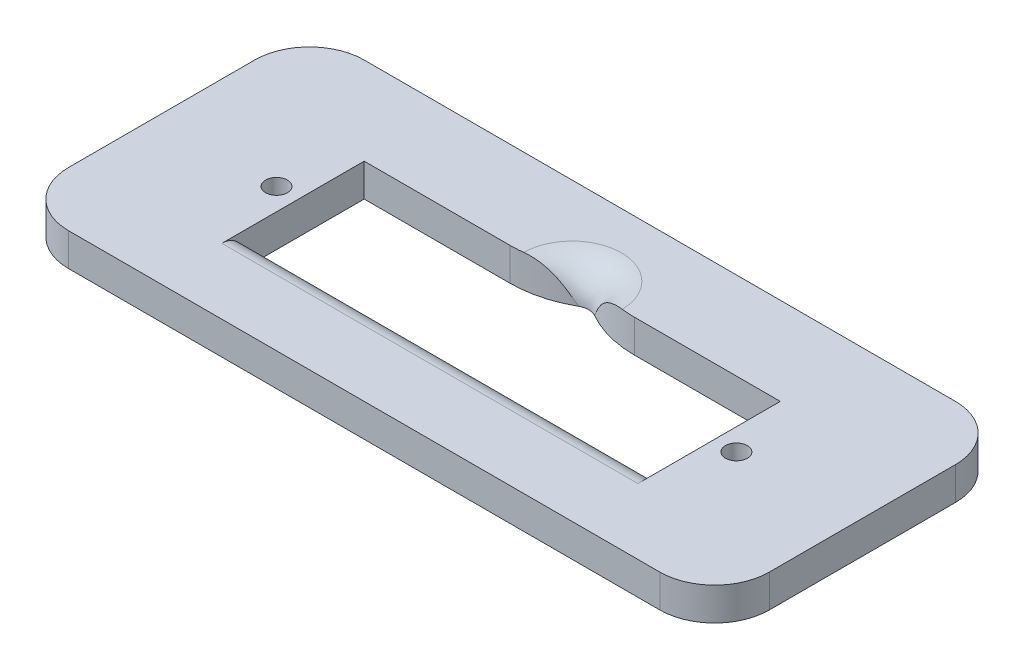
SolidWorks part; units mm, degrees
ref_plane "Front Plane" through (0, 0, 0) normal (0, 0, 1) x (1, 0, 0)
ref_plane "Top Plane" through (0, 0, 0) normal (0, 1, 0) x (1, 0, 0)
ref_plane "Right Plane" through (0, 0, 0) normal (1, 0, 0) x (0, 0, -1)
sketch "Sketch1" plane through (0, 0, 0) normal (0, 1, 0) x (1, 0, 0)
  line L0 (-32, 8.5) -> (-32, -8.5)
  line L1 (-19, 5.5) -> (19, 5.5)
  line L2 (-19, 5.5) -> (-19, -5.5)
  line L3 (-19, -5.5) -> (19, -5.5)
  line L4 (19, 5.5) -> (19, -5.5)
  line L5 (-19, 5.5) -> (19, -5.5) construction
  line L6 (-19, -5.5) -> (19, 5.5) construction
  line L7 (-27, -13.5) -> (27, -13.5)
  line L8 (32, 8.5) -> (32, -8.5)
  line L9 (-27, 13.5) -> (27, 13.5)
  line L10 (32, 18.5) -> (32, -18.5) construction
  line L11 (-32, 18.5) -> (32, 18.5) construction
  line L12 (-32, -18.5) -> (32, -18.5) construction
  line L13 (-32, 18.5) -> (-32, -18.5) construction
  arc A0 (32, 8.5) -> (27, 13.5) centre (27, 8.5) ccw
  arc A1 (27, -13.5) -> (32, -8.5) centre (27, -8.5) ccw
  arc A2 (-32, -8.5) -> (-27, -13.5) centre (-27, -8.5) ccw
  arc A3 (-32, 8.5) -> (-27, 13.5) centre (-27, 8.5) cw
  circle A4 centre (-21.006, -0.5) radius 1
  circle A5 centre (20.994, -0.5) radius 1
  point P0 (0, 0)
  dimension "D4" = 5
  dimension "D8" = 21
  dimension "D9" = 2
  dimension "D1" = 38
  dimension "D2" = 11
  dimension "D3" = 27
  dimension "D5" = 64
  dimension "D6" = 8
  dimension "D7" = 42
  dimension "D10" = 6
extrude "Main extrude" add sketch "Sketch1" along normal blind 3
sketch "Sketch2" plane through (0, 3, 0) normal (0, 1, 0) x (1, 0, 0)
  line L0 (19, 5.5) -> (-19, 5.5) construction
  circle A0 centre (0, 5.5) radius 1.5
  dimension "D1" = 3
extrude "Wire cut" cut sketch "Sketch2" against normal through all both and the other way through all
fillet "Fillet1" radius 10 2 edges at (1.5, 1.5, -5.5) (-1.5, 1.5, -5.5)
fillet "Fillet2" radius 3 1 edges at (0, 3, -7) tangent propagation no
fillet "Fillet3" radius 2 1 edges at (0, 3, 5.5)
